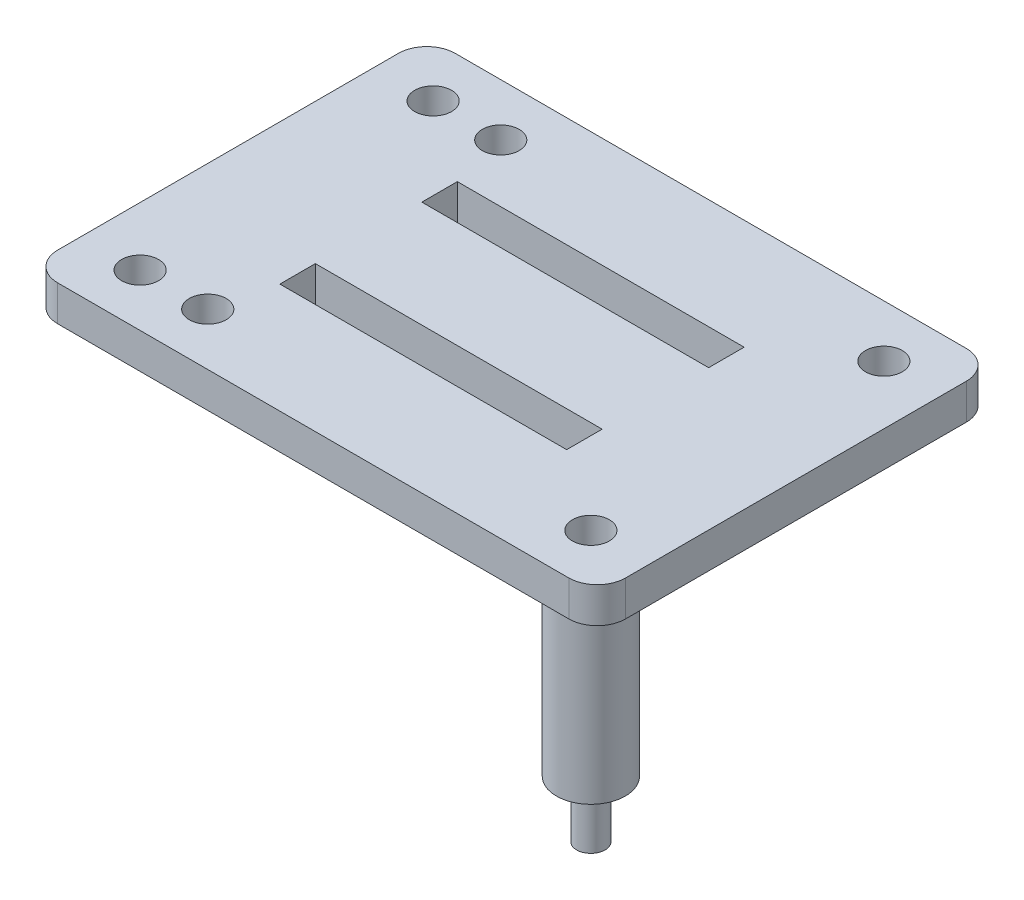
SolidWorks part; units mm, degrees
other "下垫片"
ref_plane "前视基准面" through (0, 0, 0) normal (0, 0, 1) x (1, 0, 0)
ref_plane "上视基准面" through (0, 0, 0) normal (0, 1, 0) x (1, 0, 0)
ref_plane "右视基准面" through (0, 0, 0) normal (1, 0, 0) x (0, 0, -1)
other "Configuration Table"
sketch "草图1" plane through (0, 0, 0) normal (0, 1, 0) x (1, 0, 0)
  line L0 (-89.3251, 0) -> (102.0425, 0) construction
  line L1 (0, 56.7239) -> (0, -62.578) construction
  line L2 (-20.2, -7.5) -> (20.2, -7.5)
  line L3 (-20.2, 12.5) -> (20.2, 12.5)
  line L4 (-20.2, 12.5) -> (-20.2, 7.5)
  line L5 (-20.2, 7.5) -> (20.2, 7.5)
  line L6 (20.2, 12.5) -> (20.2, 7.5)
  line L7 (-20.2, 12.5) -> (20.2, 7.5) construction
  line L8 (-20.2, 7.5) -> (20.2, 12.5) construction
  line L9 (20.2, -12.5) -> (20.2, -7.5)
  line L10 (-20.2, -12.5) -> (20.2, -12.5)
  line L11 (-20.2, -12.5) -> (-20.2, -7.5)
  circle A0 centre (-31.75, 20.6375) radius 2.6
  circle A4 centre (31.75, 20.6375) radius 2.6
  circle A5 centre (31.75, -20.6375) radius 2.6
  circle A6 centre (-31.75, -20.6375) radius 2.6
  circle A7 centre (-22.225, 20.6375) radius 2.6
  circle A8 centre (-22.225, -20.6375) radius 2.6
  point P13 (0, 10)
  dimension "D5" = 5.2
  dimension "D9" = 5.2
  dimension "D7" = 10
  dimension "D6" = 5.2
  dimension "D1" = 40.4
  dimension "D2" = 31.75
  dimension "D3" = 5
  dimension "D4" = 20.6375
  dimension "D8" = 5
  dimension "D10" = 40.4
  dimension "D11" = 8.1375
  dimension "D12" = 31.75
  dimension "D13" = 9.525
sketch "草图3" plane through (0, 0, 0) normal (0, 1, 0) x (1, 0, 0)
  line L1 (-40, -28) -> (40, -28)
  line L2 (-40, -28) -> (-40, 28)
  line L3 (-40, 28) -> (40, 28)
  line L4 (40, -28) -> (40, 28)
  line L5 (-40, -28) -> (40, 28) construction
  line L6 (-40, 28) -> (40, -28) construction
  point P0 (0, 0)
  dimension "D1" = 56
  dimension "D2" = 80
extrude "凸台-拉伸1" add sketch "草图3" along normal blind 5
extrude "切除-拉伸1" cut sketch "草图1" along normal up to surface (5 mm away) up to face at (0, 5, 0)
sketch "草图5" plane through (0, 0, 0) normal (0, -1, 0) x (1, 0, 0)
  circle A0 centre (31.75, 20.6375) radius 4.85
  dimension "D1" = 9.7
extrude "凸台-拉伸2" add sketch "草图5" along normal blind 25
sketch "草图6" plane through (0, -25, 0) normal (0, -1, 0) x (1, 0, 0)
  circle A0 centre (31.75, 20.6375) radius 2
  dimension "D1" = 4
extrude "凸台-拉伸3" add sketch "草图6" along normal blind 8
sketch "草图7" plane through (0, 5, 0) normal (0, 1, 0) x (1, 0, 0)
  line L0 (40, -28) -> (40, 28) construction
  line L1 (31.75, 20.6375) -> (50, 20.6375)
  line L2 (31.75, 20.6375) -> (31.75, -28.0079)
  line L3 (31.75, -28.0079) -> (50, -28.0079)
  line L4 (50, 20.6375) -> (50, -28.0079)
  dimension "D1" = 10
fillet "圆角2" radius 4 4 edges at (-40, 2.5, -28) (40, 2.5, -28) (40, 2.5, 28) (-40, 2.5, 28)
